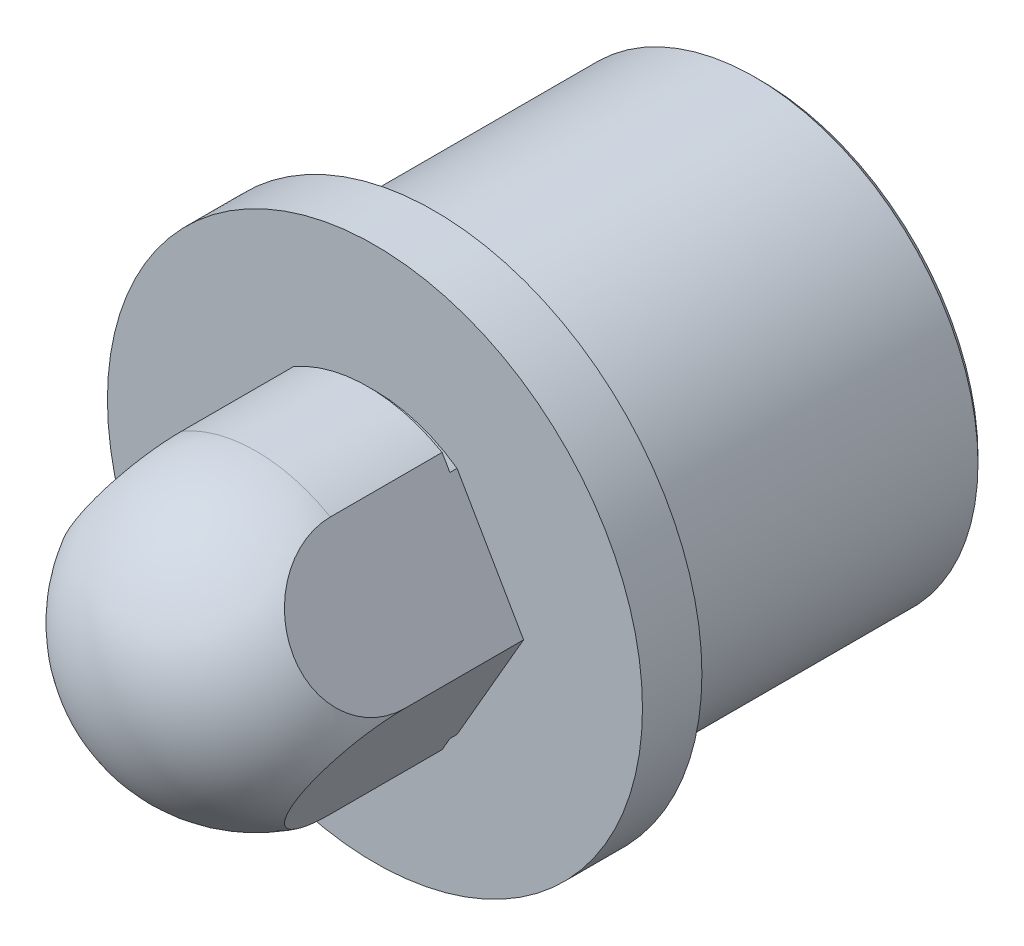
SolidWorks part; units mm, degrees
ref_plane "Front Plane" through (0, 0, 0) normal (0, 0, 1) x (1, 0, 0)
ref_plane "Top Plane" through (0, 0, 0) normal (0, 1, 0) x (1, 0, 0)
ref_plane "Right Plane" through (0, 0, 0) normal (1, 0, 0) x (0, 0, -1)
sketch "Sketch1" plane through (0, 0, 0) normal (1, 0, 0) x (0, 0, -1)
  line L1 (-11, 0) -> (11, 0) construction
  line L19 (-2, 0) -> (0, 0) construction
  line L20 (0, 0) -> (11, 0) construction
  line L22 (11, -7.5) -> (11, 7.5) construction
  line L23 (-11, -5) -> (-11, 5) construction
  line L26 (0, -9) -> (0, 9) construction
  point P5 (0, 0)
  point P11 (0, 0)
  point P15 (11, 0)
  point P16 (-11, 0)
  point P19 (11, 0)
  point P22 (0, 0)
  point P24 (-11, 0)
  point P28 (11, 0)
  dimension "ShaftDiameter" = 15
  dimension "HeadDiameter" = 10
sketch "Sketch2" plane through (0, 0, 0) normal (0, 0, 1) x (1, 0, 0)
  line L0 (-2.5, 4.3301) -> (-5, 0) construction
  line L1 (-5, 0) -> (-2.5, -4.3301) construction
  line L2 (2.5, 4.3301) -> (5, 0) construction
  line L3 (5, 0) -> (2.5, -4.3301) construction
  circle A0 centre (0, 0) radius 5 construction
  dimension "D2" = 10
  dimension "D1" = 60
sketch "Sketch3" plane through (0, 0, 0) normal (1, 0, 0) x (0, 0, -1)
  line L33 (-2, 5) -> (-2, 9)
  line L34 (-2, 9) -> (0, 9)
  line L35 (0, 9) -> (0, 7.5)
  line L36 (0.24, 7.5) -> (10.7879, 7.5)
  line L37 (11, 7.2879) -> (11, 0)
  line L38 (-11, 0) -> (11, 0) construction
  line L39 (-6, 5) -> (-2.24, 5)
  line L40 (-11, 0) -> (11, 0)
  line L41 (-2.24, 5) -> (-2.24, 4.76)
  line L42 (-2.24, 4.76) -> (-2, 4.76)
  line L43 (-2, 4.76) -> (-2, 5)
  line L45 (0, 7.5) -> (0, 7.26)
  line L46 (0, 7.26) -> (0.24, 7.26)
  line L47 (0.24, 7.26) -> (0.24, 7.5)
  line L48 (10.7879, 7.5) -> (11, 7.2879)
  arc A0 (-6, 5) -> (-11, 0) centre (-6, 0) ccw
  dimension "D2" = 0.24
  dimension "D1" = 45
  dimension "D3" = 0.3
revolve "Revolve1" add sketch "Sketch3" angle 360 about L38
sketch "Sketch5" plane through (0, 0, 2) normal (0, 0, 1) x (1, 0, 0)
  line L0 (-5, 0) -> (-2.5, -4.3301) construction
  line L1 (5, 0) -> (2.5, -4.3301) construction
  line L2 (2.5, 4.3301) -> (5, 0) construction
  line L3 (-2.5, 4.3301) -> (-5, 0) construction
  line L4 (-5, 0) -> (-2.5, -4.3301)
  line L5 (5, 0) -> (2.5, -4.3301)
  line L6 (2.5, 4.3301) -> (5, 0)
  line L7 (-2.5, 4.3301) -> (-5, 0)
  circle A0 centre (0, 0) radius 5 construction
  arc A1 (-2.5, -4.3301) -> (2.5, -4.3301) centre (0, 0) ccw
  arc A2 (2.5, 4.3301) -> (-2.5, 4.3301) centre (0, 0) ccw
extrude "Cut-Extrude1" cut sketch "Sketch5" along normal through all flip side to cut
sketch "Sketch7" plane through (0, 0, 2) normal (0, 0, 1) x (1, 0, 0)
  line L0 (-4.7384, -0.4531) -> (-2.7616, -3.877) construction
  line L1 (-2.7616, 3.877) -> (-4.7384, 0.4531) construction
  line L2 (-5, 0) -> (-4.7384, 0.4531) construction
  line L3 (-4.7384, -0.4531) -> (-5, 0) construction
  line L4 (2.7616, -3.877) -> (4.7384, -0.4531) construction
  line L5 (4.7384, 0.4531) -> (2.7616, 3.877) construction
  line L6 (5, 0) -> (4.7384, -0.4531) construction
  line L7 (4.7384, 0.4531) -> (5, 0) construction
  line L8 (-4.7384, -0.4531) -> (-2.7616, -3.877)
  line L9 (-2.7616, 3.877) -> (-4.7384, 0.4531)
  line L10 (-5, 0) -> (-4.7384, 0.4531)
  line L11 (-4.7384, -0.4531) -> (-5, 0)
  line L12 (2.7616, -3.877) -> (4.7384, -0.4531)
  line L13 (4.7384, 0.4531) -> (2.7616, 3.877)
  line L14 (5, 0) -> (4.7384, -0.4531)
  line L15 (4.7384, 0.4531) -> (5, 0)
  line L16 (-2.7616, 3.877) -> (2.7616, 3.877)
  line L17 (-2.7616, -3.877) -> (2.7616, -3.877)
  circle A1 centre (0, 0) radius 9
  circle A2 centre (0, 0) radius 9
  arc M5 (4.7384, 0.4531) -> (4.7384, -0.4531) centre (0, 0) cw
  arc M9 (-4.7384, -0.4531) -> (-4.7384, 0.4531) centre (0, 0) cw
  dimension "D1" = 0
extrude "Boss-Extrude3" add sketch "Sketch7" along normal up to surface (0.24 mm away) contours L11 L10 M9 | L15 L14 M5 region at (-4.8353, 0, 2) region at (4.8353, 0, 2) up to face at (-4.8328, 0, 2.24)
ref_plane "Contact Plane 1" through (0, 0, 11) normal (0, 0, 1) x (1, 0, 0)
ref_axis "Center Axis 1" through (0, 0, 9.35) along (0, 0, -1)
equation "\"D3@Sketch3\" = \"ShaftDiameter@Sketch1\" * .02"
equation "\"D2@Sketch2\"=\"HeadDiameter@Sketch1\""
